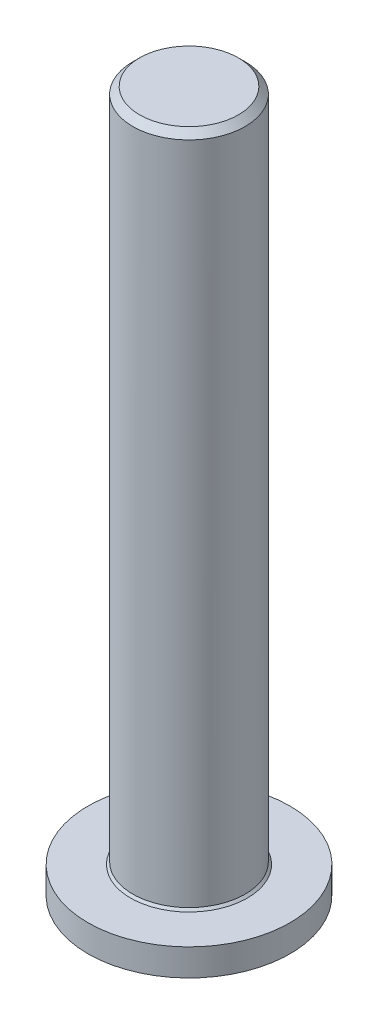
SolidWorks part; units mm, degrees
material "Alloy Steel"
ref_plane "Front Plane" through (0, 0, 0) normal (0, 0, 1) x (1, 0, 0)
ref_plane "Top Plane" through (0, 0, 0) normal (0, 1, 0) x (1, 0, 0)
ref_plane "Right Plane" through (0, 0, 0) normal (1, 0, 0) x (0, 0, -1)
sketch "Sketch2" plane through (0, 0, 0) normal (0, 1, 0) x (1, 0, 0)
  circle A0 centre (0, 0) radius 4.5
  dimension "D1" = 9
extrude "Boss-Extrude1" add sketch "Sketch2" along normal blind 1.5 contours A0
sketch "Sketch3" plane through (0, 1.5, 0) normal (0, 1, 0) x (1, 0, 0)
  circle A0 centre (0, 0) radius 2.5
  dimension "D1" = 5
extrude "Boss-Extrude2" add sketch "Sketch3" along normal blind 30
chamfer "Chamfer1" distance 0.1 angle 45 1 edges at (0, 1.5, 2.5)
chamfer "Chamfer2" distance 0.75 distance2 0.3 1 edges at (0, 0, 4.5) first distance on face at (0, 0, 4.5)
sketch "Sketch4" plane through (0, 0, 0) normal (0, -1, 0) x (1, 0, 0)
  line L1 (-0.4227, 1.6797) -> (-1.666, 0.4737)
  line L2 (-1.666, 0.4737) -> (-1.2433, -1.2059)
  line L3 (-1.2433, -1.2059) -> (0.4227, -1.6797)
  line L4 (0.4227, -1.6797) -> (1.666, -0.4737)
  line L5 (1.666, -0.4737) -> (1.2433, 1.2059)
  line L6 (1.2433, 1.2059) -> (-0.4227, 1.6797)
  circle A0 centre (0, 0) radius 1.5 construction
extrude "Cut-Extrude1" cut sketch "Sketch4" against normal blind 3
chamfer "Chamfer3" distance 0.3 angle 45 1 edges at (0, 31.5, 2.5)
ref_axis "Axis1" through (0, 31.2, 0) along (0, -1, 0)
